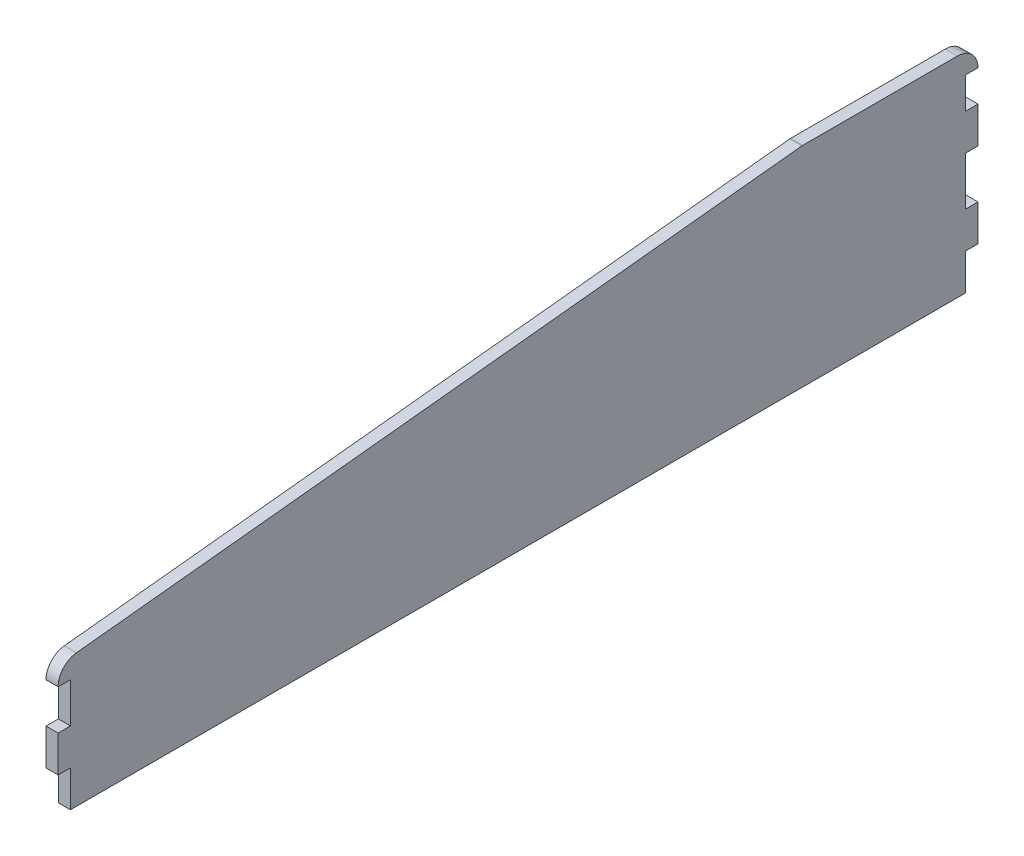
SolidWorks part; units mm, degrees
ref_plane "Front Plane" through (0, 0, 0) normal (0, 0, 1) x (1, 0, 0)
ref_plane "Top Plane" through (0, 0, 0) normal (0, 1, 0) x (1, 0, 0)
ref_plane "Right Plane" through (0, 0, 0) normal (1, 0, 0) x (0, 0, -1)
sketch "Sketch26" plane through (0, 0, 0) normal (1, 0, 0) x (0, 0, -1)
  line L0 (-76.9765, -179.6795) -> (-76.56, -179.6577)
  line L1 (-9.2968, -236.0731) -> (-4.2168, -236.0731)
  line L2 (-4.2168, -188.0912) -> (-9.2968, -188.0912)
  line L3 (-384.0425, -219.5471) -> (-378.9625, -219.5471)
  line L5 (-9.2968, -188.0912) -> (-9.2968, -201.0731)
  line L6 (-384.0425, -236.0731) -> (-378.9625, -236.0731)
  line L7 (-76.9765, -179.6795) -> (-376.4905, -211.1597)
  line L8 (-12.6503, -179.6577) -> (-76.56, -179.6577)
  line L9 (-384.0425, -236.0731) -> (-384.0425, -251.0731)
  line L10 (-378.9625, -219.5471) -> (-378.9625, -236.0731)
  line L11 (-384.0425, -251.0731) -> (-378.9625, -251.0731)
  line L12 (-378.9625, -266.0731) -> (-9.2968, -266.0731)
  line L13 (-9.2968, -216.0731) -> (-9.2968, -236.0731)
  line L14 (-378.9625, -251.0731) -> (-378.9625, -266.0731)
  line L15 (-9.2968, -251.0731) -> (-4.2168, -251.0731)
  line L16 (-4.2168, -236.0731) -> (-4.2168, -251.0731)
  line L17 (-9.2968, -201.0731) -> (-4.2168, -201.0731)
  line L18 (-9.2968, -251.0731) -> (-9.2968, -266.0731)
  line L19 (-9.2968, -216.0731) -> (-4.2168, -216.0731)
  line L20 (-4.2168, -201.0731) -> (-4.2168, -216.0731)
  arc A2 (-376.4905, -211.1597) -> (-384.0425, -219.5471) centre (-375.609, -219.5471) ccw
  arc A3 (-4.2168, -188.0912) -> (-12.6503, -179.6577) centre (-12.6503, -188.0912) ccw
  dimension "D1" = 5.08
  dimension "D2" = 5.08
  dimension "D3" = 5.08
  dimension "D4" = 15
  dimension "D5" = 15
  dimension "D6" = 15
  dimension "D7" = 20
  dimension "D8" = 15
  dimension "D9" = 15
  dimension "D10" = 5.08
  dimension "D11" = 5.08
  dimension "D12" = 77.9818
extrude "Boss-Extrude1" add sketch "Sketch26" against normal blind 5
